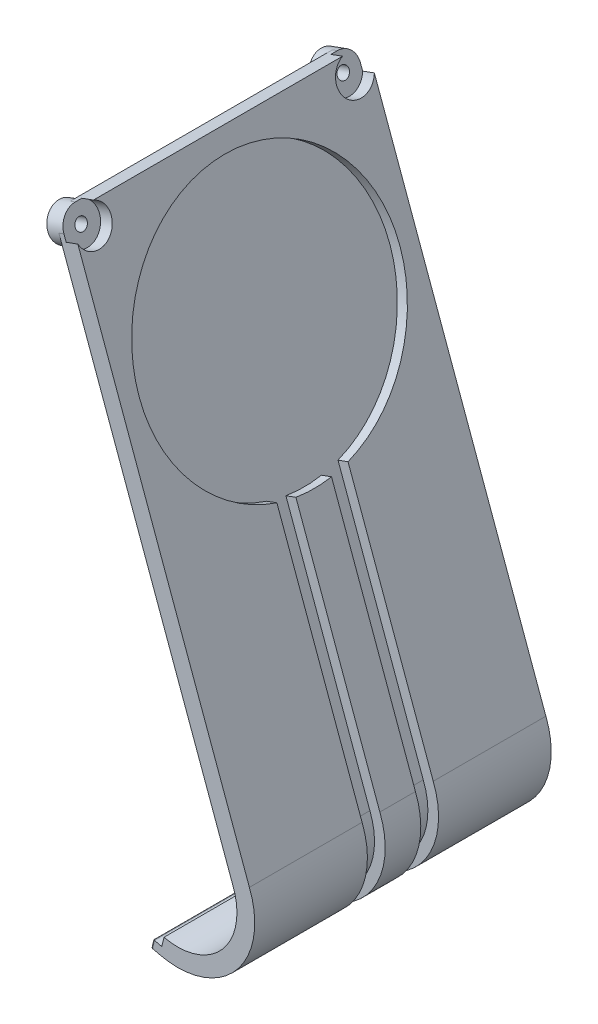
SolidWorks part; units mm, degrees
material "PLA"
ref_plane "前视基准面" through (0, 0, 0) normal (0, 0, 1) x (1, 0, 0)
ref_plane "上视基准面" through (0, 0, 0) normal (0, 1, 0) x (1, 0, 0)
ref_plane "右视基准面" through (0, 0, 0) normal (1, 0, 0) x (0, 0, -1)
other "Configuration Table"
sketch "草图2" plane through (0, 0, 0) normal (0, 0, 1) x (1, 0, 0)
  line L5 (42.7078, 13.4202) -> (12.3985, 96.6944)
  line L6 (42.7078, 13.4202) -> (9.2861, 105.2456) construction
  line L7 (31.009, 6.0497) -> (31.009, 4.5497) construction
  line L10 (15.2773, 97.8486) -> (12.3643, 96.7883) construction
  arc A0 (31.109, 0) -> (42.7078, 13.4202) centre (33.4132, 9.7309) ccw
  dimension "D3" = 0.1
  dimension "D2" = 10
  dimension "D1" = 0.1
extrude "整体拉伸-薄壁1" add sketch "草图2" along normal mid plane 50 thin thin type one direction wall 3
sketch "草图4" plane through (44.8442, 16.3219, 0) normal (0.9397, 0.342, 0) x (0, 0, -1)
  line L0 (-25, 86.6225) -> (25, 86.6225) construction
  circle A0 centre (0, 61.2225) radius 22
  dimension "D1" = 44
  dimension "D2" = 25.4
extrude "中间圆切除-拉伸1" cut sketch "草图4" against normal blind 1.8
sketch "草图3" plane through (0, 0, 0) normal (0, 0, 1) x (1, 0, 0)
  line L0 (45.5131, 14.4842) -> (15.2176, 97.7204) construction
  line L1 (45.5131, 14.4842) -> (15.2176, 97.7204) construction
  line L5 (43.8297, 13.8464) -> (29.7379, 52.5634)
  line L6 (43.8297, 13.8464) -> (13.5261, 97.1048) construction
  line L7 (31.6204, -1.2472) -> (32.3561, -1.4191) construction
  line L9 (29.7379, 52.5634) -> (31.4293, 53.179) construction
  line L16 (29.7379, 52.5634) -> (28.7118, 55.3824)
  line L17 (31.2109, -3) -> (32.0606, -3.1985) construction
  arc A0 (31.109, 0) -> (42.7078, 13.4202) centre (33.4132, 9.7309) ccw construction
  arc A1 (32.0606, -3.1985) -> (45.5131, 14.4842) centre (33.4132, 9.7309) ccw construction
  arc A2 (32.3561, -1.4191) -> (43.8297, 13.8464) centre (33.4132, 9.7309) ccw
  dimension "D2" = 3
  dimension "D1" = 1.8
extrude "线槽切除-拉伸-薄壁1" cut sketch "草图3" against normal blind 3 from offset 6 thin thin type one direction wall 1.8
mirror "镜向1" about plane through (0, 0, 0) normal (0, 0, 1) of "线槽切除-拉伸-薄壁1"
sketch "草图7" plane through (42.0251, 15.2959, 0) normal (-0.9397, -0.342, 0) x (0, 0, 1)
  line L0 (25, 86.6225) -> (-25, 86.6225) construction
  line L3 (0, 86.6225) -> (0, 71.6076) construction
  circle A0 centre (-22.1, 83.7225) radius 1
  circle A1 centre (-22.1, 83.7225) radius 2.9
  circle A2 centre (22.1, 83.7225) radius 2.9
  circle A3 centre (22.1, 83.7225) radius 1
  dimension "D1" = 2
extrude "螺丝柱凸台-拉伸2" add sketch "草图7" along normal blind 2
sketch "草图8" plane through (42.0251, 15.2959, 0) normal (-0.9397, -0.342, 0) x (0, 0, 1)
  line L0 (0, 86.6225) -> (0, 70.5485) construction
  line L1 (-26.1984, 87.8209) -> (-22.1984, 87.8209)
  line L2 (-26.1984, 87.8209) -> (-26.1984, 83.8209)
  line L3 (-26.1984, 83.8209) -> (-25.1984, 83.8209)
  line L4 (-22.1984, 87.8209) -> (-22.1984, 86.8209)
  line L5 (22.1, 86.6225) -> (-22.1, 86.6225) construction
  line L6 (22.1984, 87.8209) -> (22.1984, 86.8209)
  line L7 (26.1984, 83.8209) -> (25.1984, 83.8209)
  line L8 (26.1984, 87.8209) -> (26.1984, 83.8209)
  line L9 (26.1984, 87.8209) -> (22.1984, 87.8209)
  arc A0 (-25.1984, 83.8209) -> (-22.1984, 86.8209) centre (-22.1, 83.7225) ccw
  arc A2 (25.1984, 83.8209) -> (22.1984, 86.8209) centre (22.1, 83.7225) cw
  dimension "D2" = 4
  dimension "D3" = 4
  dimension "D4" = 1
  dimension "D5" = 1
extrude "螺丝柱切除-拉伸1" cut sketch "草图8" along normal blind 2.1 from surface starting at face at (32.5015, 50.2332, 0)
sketch "草图9" plane through (42.0251, 15.2959, 0) normal (-0.9397, -0.342, 0) x (0, 0, 1)
  line L0 (-22.1, 86.6225) -> (-25, 86.6225) construction
  line L1 (-22.1, 86.6225) -> (-25, 86.6225)
  line L2 (-25, 83.7225) -> (-25, 86.6225) construction
  line L3 (-25, 83.7225) -> (-25, 86.6225)
  line L4 (0, 86.6225) -> (0, 58.5215) construction
  line L5 (22.1, 86.6225) -> (-22.1, 86.6225) construction
  line L6 (25, 83.7225) -> (25, 86.6225)
  line L7 (22.1, 86.6225) -> (25, 86.6225)
  circle A0 centre (-22.1, 83.7225) radius 2.9 construction
  arc A1 (-22.1, 86.6225) -> (-25, 83.7225) centre (-22.1, 83.7225) ccw
  arc A2 (22.1, 86.6225) -> (25, 83.7225) centre (22.1, 83.7225) cw
extrude "螺丝使圆切除-拉伸2" cut sketch "草图9" against normal up to next
sketch "草图10" plane through (42.0251, 15.2959, 0) normal (-0.9397, -0.342, 0) x (0, 0, 1)
  circle A0 centre (22.1, 83.7225) radius 1 construction
  circle A1 centre (22.1, 83.7225) radius 1
  circle A2 centre (-22.1, 83.7225) radius 1 construction
  circle A3 centre (-22.1, 83.7225) radius 1
extrude "螺丝孔切除-拉伸3" cut sketch "草图10" against normal mid plane 5
sketch "草图11" plane through (29.4572, -6.9754, 0) normal (-0.9731, 0.2304, 0) x (0, 0, 1)
  line L0 (-25, 4.1683) -> (-25, 7.1683) construction
  line L1 (-25, 5.5683) -> (-6.1, 5.5683)
  line L2 (-25, 5.5683) -> (-25, 4.1683)
  line L3 (-25, 4.1683) -> (-6.1, 4.1683)
  line L4 (-6.1, 5.5683) -> (-6.1, 4.1683)
  line L5 (25, 4.1683) -> (-25, 4.1683) construction
  line L6 (6.1, 5.5683) -> (25, 5.5683)
  line L7 (6.1, 5.5683) -> (6.1, 4.1683)
  line L8 (6.1, 4.1683) -> (25, 4.1683)
  line L9 (25, 5.5683) -> (25, 4.1683)
  line L11 (-6, 28.3683) -> (-6, 30.1683) construction
  line L13 (6, 28.3683) -> (6, 30.1683) construction
  line L14 (25, 7.1683) -> (-25, 7.1683) construction
  dimension "D1" = 1.6
  dimension "D2" = 0.1
  dimension "D3" = 0.1
  dimension "D4" = 1.6
extrude "底部卡扣凸台-拉伸3" add sketch "草图11" along normal blind 1.5
fillet "底部卡扣圆角1" radius 0.25 8 edges at (29.2806, -1.2113, 15.55) (29.1194, -1.8925, 25) (28.9581, -2.5736, 15.55) (29.1194, -1.8925, 6.1) (29.2806, -1.2113, -15.55) (29.1194, -1.8925, -6.1) (28.9581, -2.5736, -15.55) (29.1194, -1.8925, -25)
